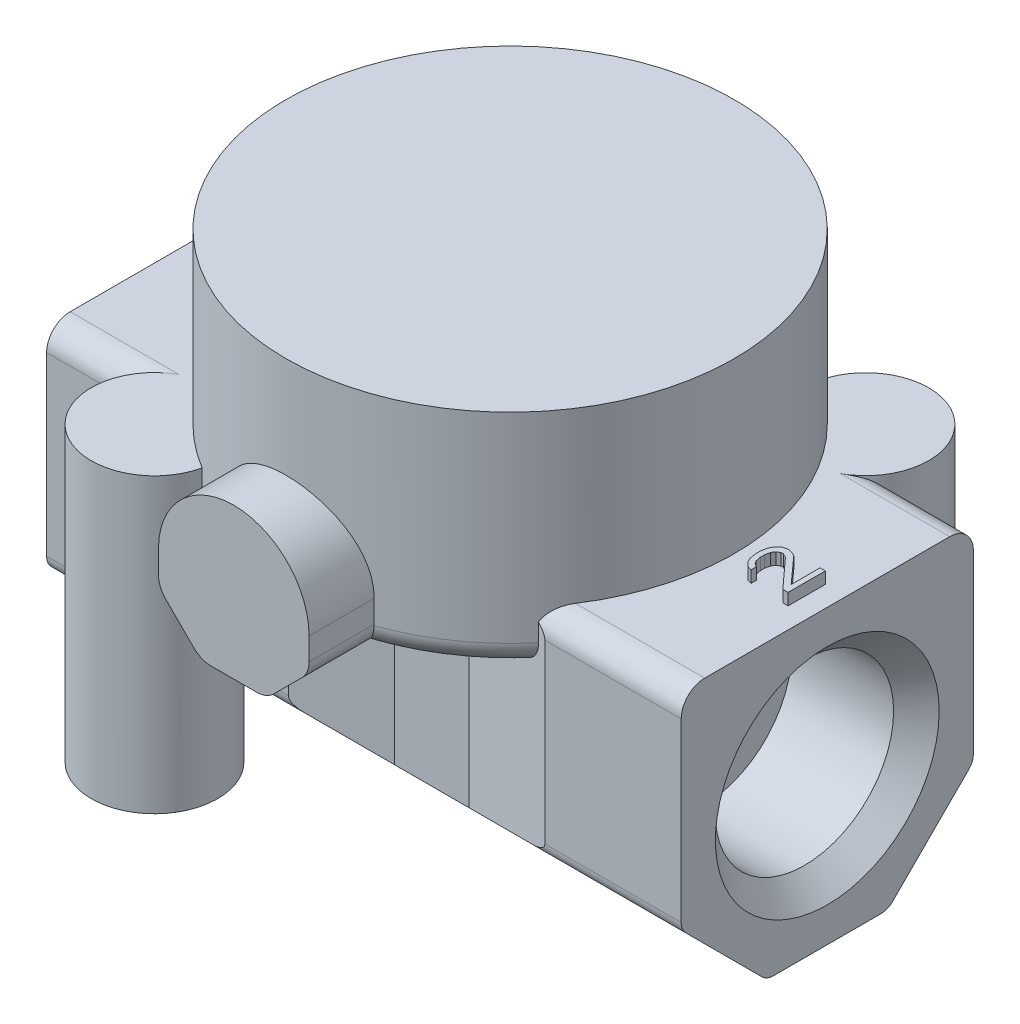
SolidWorks part; units mm, degrees
ref_plane "Front Plane" through (0, 0, 0) normal (0, 0, 1) x (1, 0, 0)
ref_plane "Top Plane" through (0, 0, 0) normal (0, 1, 0) x (1, 0, 0)
ref_plane "Right Plane" through (0, 0, 0) normal (1, 0, 0) x (0, 0, -1)
ref_plane "Plane1" through (19.8, 0, 0) normal (1, 0, 0) x (0, 0, -1)
sketch "Sketch1" plane through (19.8, 0, 0) normal (1, 0, 0) x (0, 0, -1)
  line L0 (-8.8268, -4.0864) -> (-4.0704, -8.8428)
  line L1 (-3.3633, -9.1357) -> (3.3633, -9.1357)
  line L2 (4.0704, -8.8428) -> (8.8268, -4.0864)
  line L3 (9.1197, -3.3793) -> (9.1197, 7.624)
  line L4 (7.64, 9.1037) -> (-7.65, 9.1037)
  line L5 (-9.1197, 7.634) -> (-9.1197, -3.3793)
  arc A0 (-9.1197, -3.3793) -> (-8.8268, -4.0864) centre (-8.1197, -3.3793) ccw
  arc A1 (-4.0704, -8.8428) -> (-3.3633, -9.1357) centre (-3.3633, -8.1357) ccw
  arc A2 (3.3633, -9.1357) -> (4.0704, -8.8428) centre (3.3633, -8.1357) ccw
  arc A3 (8.8268, -4.0864) -> (9.1197, -3.3793) centre (8.1197, -3.3793) ccw
  arc A4 (9.1197, 7.624) -> (7.64, 9.1037) centre (7.64, 7.624) ccw
  arc A5 (-7.65, 9.1037) -> (-9.1197, 7.634) centre (-7.65, 7.634) ccw
extrude "Boss-Extrude1" add sketch "Sketch1" against normal blind 39.612
ref_plane "Plane2" through (0, 0, 0) normal (0, 0, 1) x (1, 0, 0)
sketch "Sketch2" plane through (0, 0, 0) normal (0, 0, 1) x (1, 0, 0)
  line L0 (-11.4, -16.4478) -> (11.4, -16.4478)
  line L1 (11.4, -16.4478) -> (11.4, -9.166)
  line L2 (11.4, -9.166) -> (4.8, -7.366)
  line L3 (4.8, -7.366) -> (-4.8, -7.366)
  line L4 (-4.8, -7.366) -> (-11.4, -9.166)
  line L5 (-11.4, -9.166) -> (-11.4, -16.4478)
extrude "Cut-Extrude1" cut sketch "Sketch2" against normal blind 5.5472 and the other way blind 5.5472
ref_plane "Plane3" through (0, 0, 0) normal (0, 1, 0) x (1, 0, 0)
sketch "Sketch3" plane through (0, 0, 0) normal (0, 1, 0) x (1, 0, 0)
  line L0 (-41.3168, -33.6828) -> (43.0205, -33.6828)
  line L1 (43.0205, -33.6828) -> (43.0205, 31.7327)
  line L2 (43.0205, 31.7327) -> (-41.3168, 31.7327)
  line L3 (-41.3168, 31.7327) -> (-41.3168, -33.6828)
  line L4 (-26.1529, 16.9218) -> (-26.1529, -16.9218)
  line L5 (-26.1529, -16.9218) -> (0.1455, -7.35)
  line L6 (0.1455, -7.35) -> (4.8, -7.35)
  line L7 (4.8, -7.35) -> (30.1992, -14.2771)
  line L8 (30.1992, -14.2771) -> (30.1992, 14.2771)
  line L9 (30.1992, 14.2771) -> (4.8, 7.35)
  line L10 (4.8, 7.35) -> (0.1455, 7.35)
  line L11 (0.1455, 7.35) -> (-26.1529, 16.9218)
extrude "Cut-Extrude2" cut sketch "Sketch3" against normal blind 8.2762 and the other way blind 8.2762
ref_plane "Plane4" through (0, 0, 0) normal (1, 0, 0) x (0, 0, -1)
sketch "Sketch4" plane through (0, 0, 0) normal (1, 0, 0) x (0, 0, -1)
  line L0 (0, 19.65) -> (14, 19.65)
  line L1 (14, 19.65) -> (14, 7.15)
  line L2 (12.5, 5.65) -> (0, 5.65)
  line L3 (0, 5.65) -> (0, 19.65)
  line L4 (0, 5.65) -> (0, 19.65) construction
  arc A0 (14, 7.15) -> (12.5, 5.65) centre (12.5, 7.15) cw
revolve "Revolve1" add sketch "Sketch4" angle 360 about L4 reverse direction yes
ref_plane "Plane5" through (0, -9.166, 0) normal (0, -1, 0) x (-1, 0, 0)
sketch "Sketch5" plane through (0, -9.166, 0) normal (0, -1, 0) x (-1, 0, 0)
  circle A0 centre (11.1, -11.1) radius 3.95
extrude "Boss-Extrude2" add sketch "Sketch5" against normal blind 18.2697
ref_plane "Plane6" through (0, 0, 17.25) normal (0, 0, 1) x (1, 0, 0)
sketch "Sketch6" plane through (0, 0, 17.25) normal (0, 0, 1) x (1, 0, 0)
  line L0 (-4.7, 8.63) -> (-4.7, 7.2313)
  line L1 (-4.2536, 6.1536) -> (-2.4964, 4.3964)
  line L2 (-1.4187, 3.95) -> (1.4187, 3.95)
  line L3 (2.4964, 4.3964) -> (4.2536, 6.1536)
  line L4 (4.7, 7.2313) -> (4.7, 8.63)
  arc A0 (4.7, 8.63) -> (-4.7, 8.63) centre (0, 8.65) ccw
  arc A1 (-4.7, 7.2313) -> (-4.2536, 6.1536) centre (-3.176, 7.2313) ccw
  arc A2 (-2.4964, 4.3964) -> (-1.4187, 3.95) centre (-1.4187, 5.474) ccw
  arc A3 (1.4187, 3.95) -> (2.4964, 4.3964) centre (1.4187, 5.474) ccw
  arc A4 (4.2536, 6.1536) -> (4.7, 7.2313) centre (3.176, 7.2313) ccw
extrude "Boss-Extrude3" add sketch "Sketch6" against normal blind 20
ref_plane "Plane7" through (0, -9.166, 0) normal (0, -1, 0) x (-1, 0, 0)
sketch "Sketch7" plane through (0, -9.166, 0) normal (0, -1, 0) x (-1, 0, 0)
  circle A0 centre (-11.1, 11.1) radius 3.937
extrude "Boss-Extrude4" add sketch "Sketch7" against normal blind 18.2697
ref_plane "Plane8" through (0, 9.134, 0) normal (0, 1, 0) x (1, 0, 0)
sketch "Sketch8" plane through (0, 9.134, 0) normal (0, 1, 0) x (1, 0, 0)
  line L0 (-15.2, -0.265) -> (-15.2, 0.1225)
  line L1 (-15.2, 0.1225) -> (-15.6617, 0.51)
  line L2 (-15.6617, 0.51) -> (-16.1894, 0.51)
  line L3 (-16.1894, 0.51) -> (-15.7277, 0.1225)
  line L4 (-15.7277, 0.1225) -> (-18.3, 0.1225)
  line L5 (-18.3, 0.1225) -> (-18.3, -0.265)
  line L6 (-18.3, -0.265) -> (-15.2, -0.265)
extrude "Boss-Extrude5" add sketch "Sketch8" against normal blind 0.7 and the other way blind 0.7
ref_plane "Plane9" through (0, 9.134, 0) normal (0, 1, 0) x (1, 0, 0)
sketch "Sketch9" plane through (0, 9.134, 0) normal (0, 1, 0) x (1, 0, 0)
  line L0 (18.5, -1.143) -> (18.5, 1.182)
  line L1 (18.5, 1.182) -> (18.1702, 1.182)
  line L2 (18.1702, 1.182) -> (18.1702, -0.6263)
  line L3 (18.1702, -0.6263) -> (16.7191, 0.9882)
  line L4 (16.7191, 0.9882) -> (16.5213, 1.1174)
  line L5 (16.5213, 1.1174) -> (16.2574, 1.182)
  line L6 (16.2574, 1.182) -> (16.1255, 1.182)
  line L7 (16.1255, 1.182) -> (15.8617, 1.1174)
  line L8 (15.8617, 1.1174) -> (15.5979, 0.8591)
  line L9 (15.5979, 0.8591) -> (15.466, 0.6008)
  line L10 (15.466, 0.6008) -> (15.4, 0.2132)
  line L11 (15.4, 0.2132) -> (15.4, -0.0451)
  line L12 (15.4, -0.0451) -> (15.466, -0.4972)
  line L13 (15.466, -0.4972) -> (15.5979, -0.7555)
  line L14 (15.5979, -0.7555) -> (15.8617, -1.0138)
  line L15 (15.8617, -1.0138) -> (16.1255, -1.0784)
  line L16 (16.1255, -1.0784) -> (16.1255, -0.7555)
  line L17 (16.1255, -0.7555) -> (15.9277, -0.6263)
  line L18 (15.9277, -0.6263) -> (15.7957, -0.4326)
  line L19 (15.7957, -0.4326) -> (15.7298, -0.1097)
  line L20 (15.7298, -0.1097) -> (15.7298, 0.1487)
  line L21 (15.7298, 0.1487) -> (15.7957, 0.4716)
  line L22 (15.7957, 0.4716) -> (15.9277, 0.6653)
  line L23 (15.9277, 0.6653) -> (16.1255, 0.7945)
  line L24 (16.1255, 0.7945) -> (16.2574, 0.7945)
  line L25 (16.2574, 0.7945) -> (16.5213, 0.6653)
  line L26 (16.5213, 0.6653) -> (18.1702, -1.143)
  line L27 (18.1702, -1.143) -> (18.5, -1.143)
extrude "Boss-Extrude6" add sketch "Sketch9" against normal blind 0.7 and the other way blind 0.7
ref_plane "Plane10" through (0, 0, -11.1) normal (0, 0, -1) x (-1, 0, 0)
sketch "Sketch10" plane through (0, 0, -11.1) normal (0, 0, -1) x (-1, 0, 0)
  line L0 (-11.1125, -9.166) -> (-13.97, -9.166)
  line L1 (-13.97, -9.166) -> (-13.208, -8.404)
  line L2 (-13.208, -8.404) -> (-13.208, 0.484)
  line L3 (-13.208, 0.484) -> (-11.1125, 1.7431)
  line L4 (-11.1125, 1.7431) -> (-11.1125, -9.166)
  line L5 (-11.1125, 1.7432) -> (-11.1125, -9.166) construction
revolve "Cut-Revolve1" cut sketch "Sketch10" angle 360 about L5 reverse direction yes
ref_plane "Plane11" through (0, 0, 11.1) normal (0, 0, -1) x (-1, 0, 0)
sketch "Sketch11" plane through (0, 0, 11.1) normal (0, 0, -1) x (-1, 0, 0)
  line L0 (11.1125, -9.166) -> (8.317, -9.166)
  line L1 (8.317, -9.166) -> (9.0455, -8.4375)
  line L2 (9.0455, -8.4375) -> (9.0455, 0.5011)
  line L3 (9.0455, 0.5011) -> (11.1125, 1.7431)
  line L4 (11.1125, 1.7431) -> (11.1125, -9.166)
  line L5 (11.1125, 1.7432) -> (11.1125, -9.166) construction
revolve "Cut-Revolve2" cut sketch "Sketch11" angle 360 about L5 reverse direction yes
ref_plane "Plane12" through (0, 0, 0) normal (0, 0, -1) x (-1, 0, 0)
sketch "Sketch12" plane through (0, 0, 0) normal (0, 0, -1) x (-1, 0, 0)
  line L0 (12, 0) -> (12, 5.4991)
  line L1 (12, 5.4991) -> (18.3111, 5.4991)
  line L2 (18.3111, 5.4991) -> (19.812, 7)
  line L3 (19.812, 7) -> (19.812, 0)
  line L4 (19.812, 0) -> (12, 0)
  line L5 (19.812, 0) -> (12, 0) construction
revolve "Cut-Revolve3" cut sketch "Sketch12" angle 360 about L5 reverse direction yes
ref_plane "Plane13" through (0, 0, 0) normal (0, 0, -1) x (-1, 0, 0)
sketch "Sketch13" plane through (0, 0, 0) normal (0, 0, -1) x (-1, 0, 0)
  line L0 (-19.8, 0) -> (-19.8, 6.985)
  line L1 (-19.8, 6.985) -> (-18.3776, 5.5626)
  line L2 (-18.3776, 5.5626) -> (-12, 5.5626)
  line L3 (-12, 5.5626) -> (-12, 0)
  line L4 (-12, 0) -> (-19.8, 0)
  line L5 (-12, 0) -> (-19.8, 0) construction
revolve "Cut-Revolve4" cut sketch "Sketch13" angle 360 about L5 reverse direction yes
